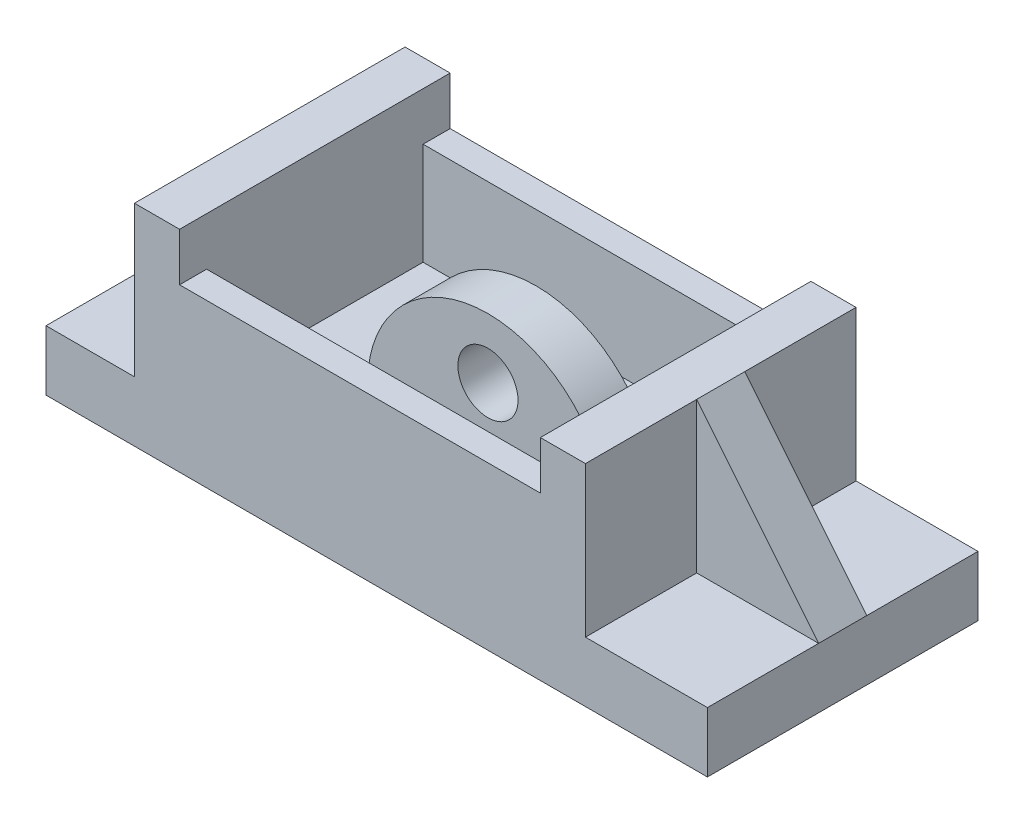
SolidWorks part; units mm, degrees
ref_plane "Front Plane" through (0, 0, 0) normal (0, 0, 1) x (1, 0, 0)
ref_plane "Top Plane" through (0, 0, 0) normal (0, 1, 0) x (1, 0, 0)
ref_plane "Right Plane" through (0, 0, 0) normal (1, 0, 0) x (0, 0, -1)
sketch "Sketch3" plane through (0, 0, 0) normal (0, 1, 0) x (1, 0, 0)
  line L0 (-40.2846, 22.5) -> (-40.2846, -22.5)
  line L1 (55, -22.5) -> (-55, -22.5)
  line L2 (55, -22.5) -> (55, 22.5)
  line L3 (55, 22.5) -> (-55, 22.5)
  line L4 (-55, -22.5) -> (-55, 22.5)
  line L5 (55, -22.5) -> (-55, 22.5) construction
  line L6 (55, 22.5) -> (-55, -22.5) construction
  line L7 (34.7154, 22.5) -> (34.7154, -22.5)
  line L8 (-32.7846, 22.5) -> (-32.7846, -22.5)
  line L9 (27.2154, 22.5) -> (27.2154, -22.5)
  line L10 (-32.7846, 18) -> (27.2154, 18)
  line L11 (-32.7846, -18) -> (27.2154, -18)
  point P0 (0, 0)
  dimension "D1" = 110
  dimension "D2" = 45
  dimension "D3" = 75
  dimension "D6" = 4.5
  dimension "D7" = 4.5
  dimension "D4" = 7.5
  dimension "D5" = 7.5
extrude "Boss-Extrude4" add sketch "Sketch3" along normal blind 10 contours L4 L1 L0 L3 | L8 L11 L9 L10 | L3 L7 L1 L2 region at (-47.6423, 0, 0) region at (-2.7846, 0, 0) region at (44.8577, 0, 0)
extrude "Boss-Extrude5" add sketch "Sketch3<3>" along normal blind 35 contours L8 L3 L0 L1 | L3 L9 L1 L7 region at (-36.5346, 0, 0) region at (30.9654, 0, 0)
sketch "Sketch3<3>" plane through (0, 0, 0) normal (0, 1, 0) x (1, 0, 0) same geometry as "Sketch3"
extrude "Boss-Extrude6" add sketch "Sketch3<4>" along normal blind 27 contours L11 L8 L1 L9 | L8 L10 L9 L3 region at (-2.7846, 0, -20.25) region at (-2.7846, 0, 20.25)
sketch "Sketch3<4>" plane through (0, 0, 0) normal (0, 1, 0) x (1, 0, 0) same geometry as "Sketch3"
sketch "Sketch4" plane through (0, 0, 0) normal (0, 0, 1) x (1, 0, 0)
  line L0 (-20, 10) -> (20, 10)
  arc A0 (20, 10) -> (-20, 10) centre (0, 10) ccw
  circle A1 centre (0, 20) radius 5
  dimension "D1" = 40
  dimension "D3" = 10
  dimension "D2" = 10
  dimension "D4" = 20
extrude "Boss-Extrude7" add sketch "Sketch4" along normal mid plane 8
sketch "Sketch5" plane through (0, 0, 0) normal (0, 0, 1) x (1, 0, 0)
  line L0 (-40.2846, 35) -> (-55, 10)
rib "Rib1" sketch "Sketch5" sketch "Sketch5" thickness 8 extrusion direction parallel to sketch draft on no parameters "D1"=8
sketch "Sketch6" plane through (0, 0, 0) normal (0, 0, 1) x (1, 0, 0)
  line L0 (34.7154, 35) -> (55, 10)
rib "Rib2" sketch "Sketch6" sketch "Sketch6" thickness 8 extrusion direction parallel to sketch draft on no parameters "D1"=8
